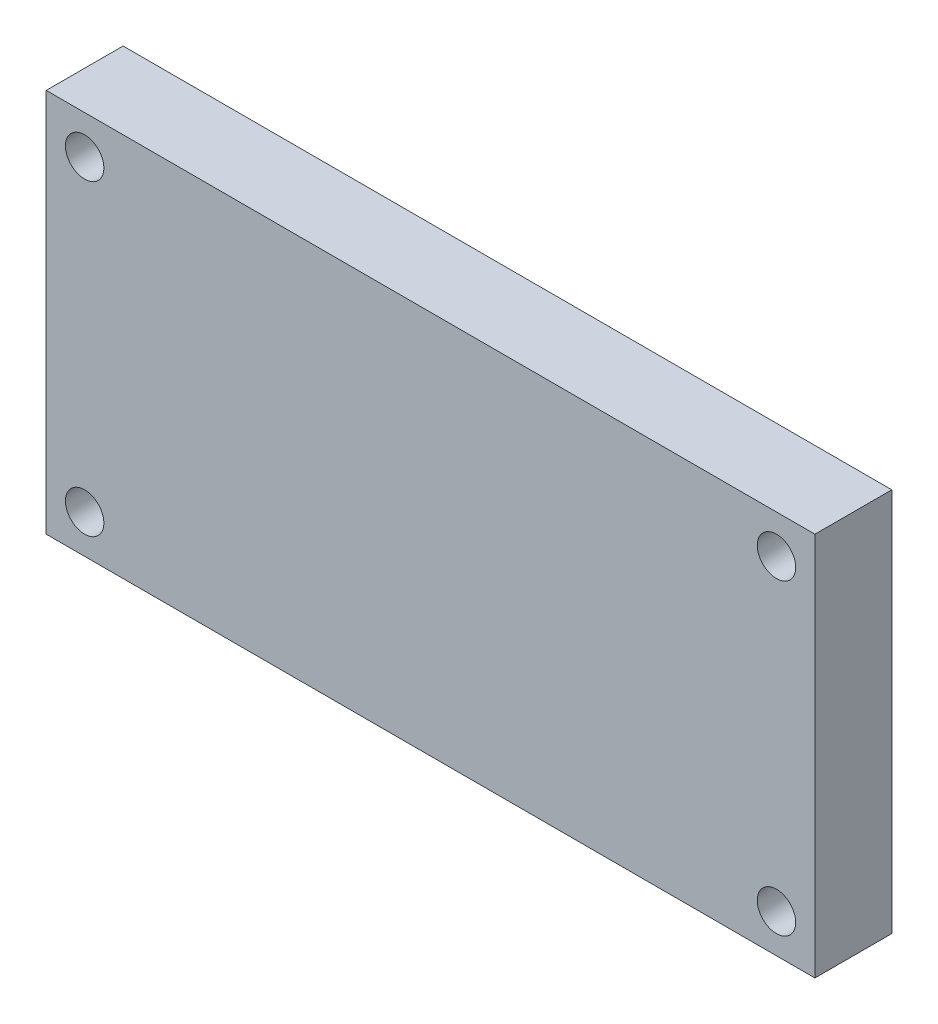
SolidWorks part; units mm, degrees
material "Alumina"
ref_plane "Front Plane" through (0, 0, 0) normal (0, 0, 1) x (1, 0, 0)
ref_plane "Top Plane" through (0, 0, 0) normal (0, 1, 0) x (1, 0, 0)
ref_plane "Right Plane" through (0, 0, 0) normal (1, 0, 0) x (0, 0, -1)
sketch "Sketch1" plane through (0, 0, 0) normal (0, 0, 1) x (1, 0, 0)
  line L1 (0, 0) -> (100, 0)
  line L2 (0, 0) -> (0, 50)
  line L3 (0, 50) -> (100, 50)
  line L4 (100, 0) -> (100, 50)
  circle A0 centre (5, 5) radius 2.5
  circle A1 centre (5, 45) radius 2.5
  circle A2 centre (95, 45) radius 2.5
  circle A3 centre (95, 5) radius 2.5
  dimension "D3" = 5
  dimension "D8" = 5
  dimension "D1" = 100
  dimension "D2" = 50
  dimension "D4" = 5
  dimension "D5" = 5
  dimension "D6" = 5
  dimension "D7" = 5
  dimension "D9" = 5
  dimension "D10" = 5
  dimension "D11" = 5
extrude "Boss-Extrude1" add sketch "Sketch1" along normal mid plane 10 contours L3 L4 L1 L2 | A0 | A3 | A2 | A1
sketch "Sketch2" plane through (0, 0, -5) normal (0, 0, -1) x (-1, 0, 0)
  line L0 (-100, 0) -> (-100, 50) construction
  line L1 (-60, 30) -> (-40, 30)
  line L2 (-60, 30) -> (-60, 20)
  line L3 (-60, 20) -> (-40, 20)
  line L4 (-40, 30) -> (-40, 20)
  line L5 (-59, 29) -> (-50.5, 29)
  line L6 (-59, 29) -> (-59, 21)
  line L7 (-59, 21) -> (-50.5, 21)
  line L8 (-50.5, 29) -> (-50.5, 21)
  line L9 (-49.5, 29) -> (-41, 29)
  line L10 (-49.5, 29) -> (-49.5, 21)
  line L11 (-49.5, 21) -> (-41, 21)
  line L12 (-41, 29) -> (-41, 21)
  line L14 (0, 50) -> (-100, 50) construction
  dimension "D1" = 20
  dimension "D2" = 10
  dimension "D3" = 1
  dimension "D4" = 1
  dimension "D5" = 1
  dimension "D6" = 1
  dimension "D7" = 8.5
  dimension "D8" = 8.5
  dimension "D9" = 40
  dimension "D10" = 20
extrude "Boss-Extrude2" add sketch "Sketch2" along normal blind 2 contours L9 L12 L11 L10 | L5 L8 L7 L6 | L1 L4 L3 L2
extrude "Boss-Extrude3" add sketch "Sketch2<3>" along normal blind 3 contours L10 L11 L12 L9 | L8 L7 L6 L5
sketch "Sketch2<3>" plane through (0, 0, -5) normal (0, 0, -1) x (-1, 0, 0) same geometry as "Sketch2"
